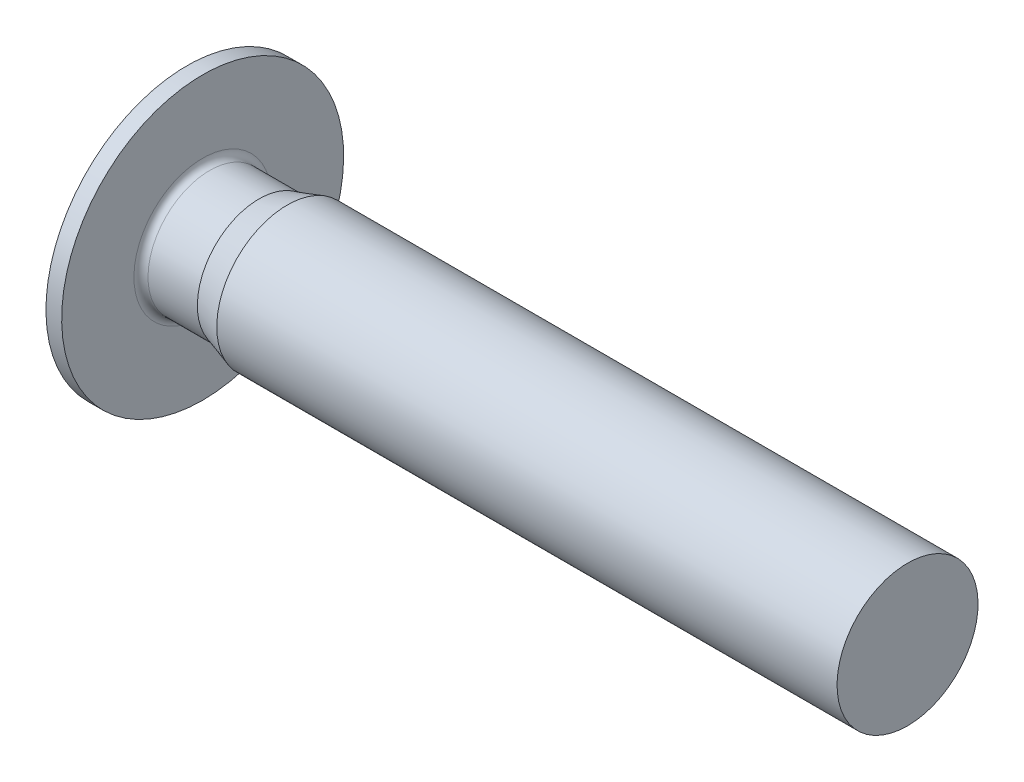
SolidWorks part; units mm, degrees
material "SCM435"
ref_plane "Front Plane" through (0, 0, 0) normal (0, 0, 1) x (1, 0, 0)
ref_plane "Top Plane" through (0, 0, 0) normal (0, 1, 0) x (1, 0, 0)
ref_plane "Right Plane" through (0, 0, 0) normal (1, 0, 0) x (0, 0, -1)
sketch "Sketch1" plane through (0, 0, 0) normal (0, 0, 1) x (1, 0, 0)
  line L0 (-0.5, 0) -> (10, 0) construction
  line L1 (-0.5, 0) -> (-0.5, 1.52)
  line L2 (-0.2229, 2) -> (0, 2)
  line L3 (0, 2) -> (0, 0.875)
  line L4 (1.2, 1) -> (10, 1)
  line L5 (10, 1) -> (10, 0)
  line L6 (10, 0) -> (-0.5, 0)
  line L7 (1.2, 1) -> (0.8, 0.875)
  line L8 (0.8, 0.875) -> (0, 0.875)
  line L9 (-0.2229, 2) -> (-0.5, 1.52)
  line L10 (-0.5, 0) -> (10, 0) construction
  dimension "A" = 4
  dimension "M" = 2
  dimension "L" = 10
  dimension "MSM_1" = 3.04
  dimension "E_s" = 1.2
  dimension "E" = 0.5
  dimension "FIX_1" = 30
  dimension "MSM_2" = 1.75
  dimension "MSM_3" = 0.4
revolve "Revolve1" add sketch "Sketch1" angle 360 about L0
cosmetic thread "Thread1" parameters "ATL_1"=8.8, "ATD"=1.567
fillet "Fillet1" radius 0.1 1 edges at (0, -0.875, 0)
sketch "Sketch2" plane through (-0.5, 0, 0) normal (-1, 0, 0) x (0, 0, 1)
  line L1 (0, 0.7506) -> (-0.65, 0.3753)
  line L2 (-0.65, 0.3753) -> (-0.65, -0.3753)
  line L3 (-0.65, -0.3753) -> (0, -0.7506)
  line L4 (0, -0.7506) -> (0.65, -0.3753)
  line L5 (0.65, -0.3753) -> (0.65, 0.3753)
  line L6 (0.65, 0.3753) -> (0, 0.7506)
  circle A0 centre (0, 0) radius 0.65 construction
  dimension "B" = 1.3
extrude "Cut-Extrude1" cut sketch "Sketch2" against normal blind 1.2
sketch "Sketch3" plane through (0, 0, 0) normal (0, 0, 1) x (1, 0, 0)
  line L0 (0.7, 0) -> (1.0906, 0) construction
  line L1 (0.7, 0) -> (0.7, 0.65)
  line L2 (0.7, 0.65) -> (1.0906, 0)
  line L3 (1.0906, 0) -> (0.7, 0)
  line L5 (0.7, 0.3753) -> (0.7, -0.3753) construction
  dimension "FIX_3" = 59
  dimension "B" = 1.3
revolve "Cut-Revolve1" cut sketch "Sketch3" angle 360 about L0
equation "\"ATL_1@Thread1\" = \"L@Sketch1\" - \"E_s@Sketch1\""
